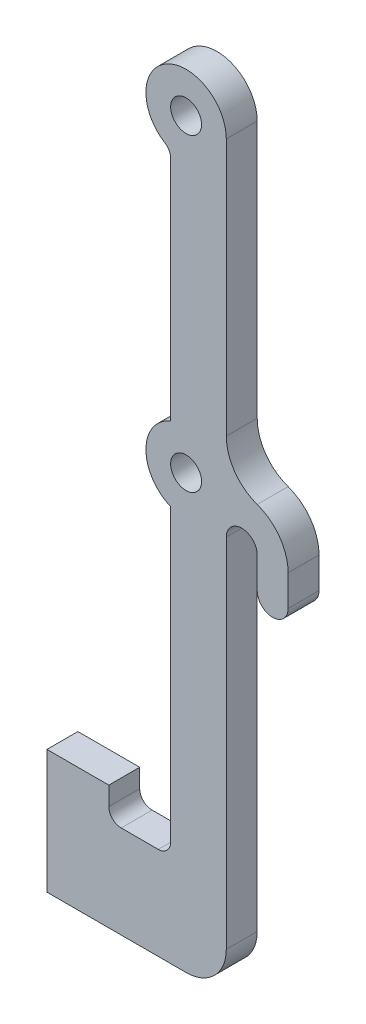
SolidWorks part; units mm, degrees
ref_plane "Front Plane" through (0, 0, 0) normal (0, 0, 1) x (1, 0, 0)
ref_plane "Top Plane" through (0, 0, 0) normal (0, 1, 0) x (1, 0, 0)
ref_plane "Right Plane" through (0, 0, 0) normal (1, 0, 0) x (0, 0, -1)
sketch "Sketch1" plane through (0, 0, 0) normal (0, 0, 1) x (1, 0, 0)
  line L0 (8.255, 0) -> (8.255, -144.145)
  line L1 (-3.175, -7.62) -> (-3.175, -55.88)
  line L2 (-5.715, -133.35) -> (-13.335, -133.35)
  line L3 (-15.875, -130.81) -> (-15.875, -127)
  line L4 (-15.875, -127) -> (-28.575, -127)
  line L5 (-28.575, -127) -> (-28.575, -152.4)
  line L6 (0, 0) -> (0, -144.145) construction
  line L7 (0, -152.4) -> (-28.575, -152.4)
  line L8 (-3.175, -71.12) -> (-3.175, -130.81)
  arc A0 (8.255, 0) -> (-3.175, -7.62) centre (0, 0) ccw
  circle A1 centre (0, 0) radius 3.175
  arc A3 (-13.335, -133.35) -> (-15.875, -130.81) centre (-13.335, -130.81) cw
  arc A4 (-5.715, -133.35) -> (-3.175, -130.81) centre (-5.715, -130.81) ccw
  circle A5 centre (0, -144.145) radius 3.175 construction
  arc A6 (8.255, -144.145) -> (0, -152.4) centre (0, -144.145) cw
  circle A7 centre (0, -63.5) radius 3.175
  arc A8 (-3.175, -55.88) -> (-3.175, -71.12) centre (0, -63.5) ccw
  circle A9 centre (0, -63.5) radius 8.255 construction
  dimension "D1" = 16.51
  dimension "D2" = 2.54
  dimension "D4" = 6.35
  dimension "D7" = 6.35
  dimension "D3" = 12.7
  dimension "D9" = 63.5
  dimension "D5" = 152.4
  dimension "D6" = 6.35
  dimension "D8" = 25.4
  dimension "D12" = 12.7
  dimension "D13" = 6.35
extrude "Boss-Extrude1" add sketch "Sketch1" along normal mid plane 6.35 contours A8 L8 A4 L2 A3 L3 L4 L5 L7 A6 L0 region at (-2.3168, -87.4338, 0)
fillet "Fillet1" radius 2.54 1 edges at (-3.175, -7.62, 0)
sketch "Sketch2" plane through (0, 0, 3.175) normal (0, 0, 1) x (1, 0, 0)
  line L1 (14.605, -70.8224) -> (14.605, -77.1724)
  line L2 (8.255, 0) -> (8.255, -144.145) construction
  line L3 (20.955, -77.1724) -> (20.955, -70.8224)
  line L4 (8.255, -52.8619) -> (8.255, -70.8224)
  arc A0 (14.605, -70.8224) -> (8.255, -70.8224) centre (11.43, -70.8224) ccw
  arc A2 (14.605, -77.1724) -> (20.955, -77.1724) centre (17.78, -77.1724) ccw
  arc A3 (20.955, -70.8224) -> (14.605, -61.8422) centre (11.43, -70.8224) ccw
  arc A4 (14.605, -61.8422) -> (8.255, -52.8619) centre (17.78, -52.8619) cw
  dimension "D3" = 3.175
  dimension "D4" = 3.175
  dimension "D1" = 6.35
  dimension "D2" = 6.35
extrude "Boss-Extrude2" add sketch "Sketch2" against normal blind 6.35
